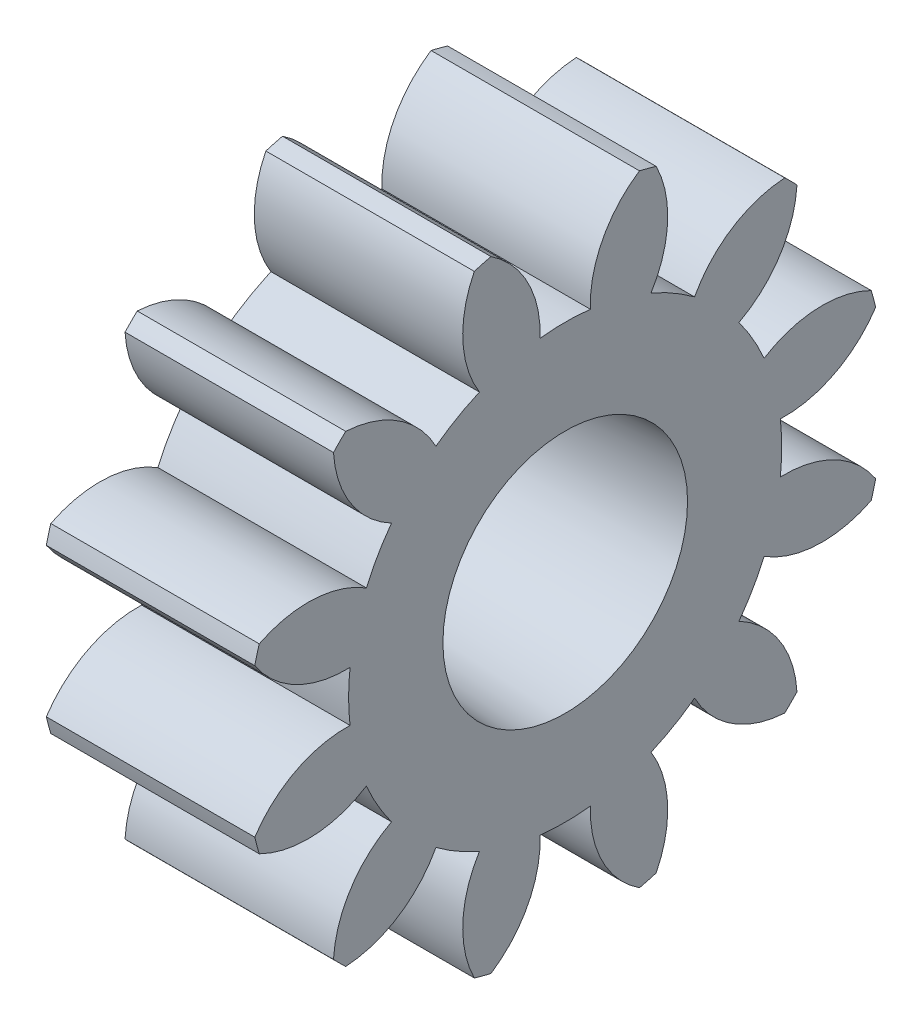
SolidWorks part; units mm, degrees
ref_plane "Plane1" through (0, 0, 0) normal (0, 0, 1) x (1, 0, 0)
ref_plane "Plane2" through (0, 0, 0) normal (0, 1, 0) x (1, 0, 0)
ref_plane "Plane3" through (0, 0, 0) normal (1, 0, 0) x (0, 0, -1)
other "Configuration Table"
sketch "HoldingSke" plane through (0, 0, 0) normal (0, 1, 0) x (1, 0, 0)
  line L0 (0, 0) -> (0.5589, -0.1188)
  line L1 (-15, 0) -> (100, 0) construction
  line L2 (0, 0) -> (-2.1039, 2.3779)
  line L3 (0, 0) -> (-11.863, 4.5341)
  line L4 (0, 0) -> (8.4473, 1.7955)
  line L5 (0, 0) -> (-14.9912, -5.5913)
  line L6 (0, 0) -> (-6.6317, -4.4744)
  line L7 (-2.1039, 2.3779) -> (1.3401, 18.0029)
  line L8 (-76.2, 54.61) -> (-74.8, 54.61)
  line L9 (-71.009, 38.7566) -> (-53.1078, 45.2721)
  line L10 (-76.2, 71.12) -> (104.1128, 71.12)
  line L11 (0, 0) -> (-8, 0)
  line L12 (-76.2, 101.6) -> (-76.147, 101.6)
  line L13 (24.9733, 27.94) -> (52.9518, 28.4284)
  line L14 (24.9733, 27.94) -> (24.9743, 27.94)
  line L15 (24.9733, 27.94) -> (100.4006, 29.5858)
  line L16 (-63.627, -1.75) -> (-12.827, -1.75)
  circle A0 centre (0, 0) radius 4.5
  circle A1 centre (0, 0) radius 8.3115
  circle A2 centre (0, 0) radius 37.5
  circle A3 centre (0, 0) radius 4.5
  dimension "Num_teeth" = 12
  dimension "Pitch_radius" = 180.3128
  dimension "Width" = 8
  dimension "Thickness" = 8
sketch "BasProSke" plane through (0, 0, 0) normal (0, 1, 0) x (1, 0, 0)
  line L0 (-10, 0) -> (60, 0) construction
  line L1 (0, 0) -> (0, 12.25)
  line L2 (0, 0) -> (8, 0)
  line L3 (8, 0) -> (8, 12.25)
  line L4 (8, 12.25) -> (0, 12.25)
  dimension "Thickness" = 8
  dimension "Diameter" = 24.5
revolve "Base-Revolve" add sketch "BasProSke" angle 360 about L0
sketch "TooCutSke" plane through (0, 0, 0) normal (1, 0, 0) x (0, 0, -1)
  line L1 (0, 0) -> (0, 107) construction
  line L2 (0, 0) -> (-1.4632, 10.3976) construction
  line L3 (0, 0) -> (-5.3948, 20.1337) construction
  line L4 (-1.4632, 10.3976) -> (-2.6974, 10.0668) construction
  arc A0 (0.9651, 8.2553) -> (-0.9651, 8.2553) centre (0, 0) ccw
  arc A1 (2.8783, 11.9332) -> (-2.8783, 11.9332) centre (0, 0) ccw
  circle A2 centre (0, 0) radius 10.5 construction
  circle A3 centre (0, 0) radius 9.8668 construction
  arc A4 (-0.9651, 8.2553) -> (-2.8783, 11.9332) centre (-5.1623, 8.4085) ccw
  arc A5 (2.8783, 11.9332) -> (0.9651, 8.2553) centre (5.1623, 8.4085) ccw
extrude "ToothCut" cut sketch "TooCutSke" along normal through all
fillet "Breaks" [suppressed] radius 0.035 tangent propagation no
fillet "RootFillets" [suppressed] radius 0.4385
pattern_circular "TeethCuts" count 12 every 30 about axis through (-10, 0, 0) along (1, 0, 0) of "ToothCut", "RootFillets", "Breaks"
sketch "HubNeaOneSke" plane through (0, 0, 0) normal (-1, 0, 0) x (0, 0, 1)
  circle A0 centre (0, 0) radius 8.3115
  dimension "Diameter" = 16.623
extrude "HubNearOne" add sketch "HubNeaOneSke" along normal blind 8.0001
sketch "HubNeaBotSke" plane through (0, 0, 0) normal (-1, 0, 0) x (0, 0, 1)
  circle A0 centre (0, 0) radius 8.3115
  dimension "Diameter" = 16.623
extrude "HubNearBoth" [suppressed] add sketch "HubNeaBotSke" along normal blind 4
ref_plane "FarPln" through (8, 0, 0) normal (1, 0, 0) x (0, 0, -1)
sketch "HubFarSke" plane through (8, 0, 0) normal (1, 0, 0) x (0, 0, -1)
  circle A0 centre (0, 0) radius 8.3115
  dimension "Diameter" = 16.623
extrude "HubFar" [suppressed] add sketch "HubFarSke" along normal blind 4
sketch "BorSke" plane through (0, 0, 0) normal (1, 0, 0) x (0, 0, -1)
  circle A0 centre (0, 0) radius 4.5
  dimension "Diameter" = 9
extrude "Bore" cut sketch "BorSke" along normal mid plane 32.0001
sketch "KeySke" plane through (0, 0, 0) normal (1, 0, 0) x (0, 0, -1)
  line L0 (-1.5, 0) -> (-1.5, 5.9)
  line L1 (-1.5, 5.9) -> (1.5, 5.9)
  line L2 (1.5, 5.9) -> (1.5, 0)
  line L3 (0, 0) -> (0, 34) construction
  line L4 (-1.5, 0) -> (1.5, 0)
  dimension "Width" = 3
extrude "Keyway" [suppressed] cut sketch "KeySke" along normal mid plane 32.0001
pattern_circular "Keyway2" [suppressed] count 2 every 90 about axis through (-10, 0, 0) along (1, 0, 0) reverse direction yes
sketch "Esquisse1" plane through (-8.0001, 0, 0) normal (-1, 0, 0) x (0, 0, 1)
  circle A0 centre (0, 0) radius 8.3115
extrude "Enlèv. mat.-Extru.1" cut sketch "Esquisse1" against normal blind 8
sketch "Esquisse2" plane through (8, 0, 0) normal (1, 0, 0) x (0, 0, -1)
  circle A0 centre (0, 0) radius 4.275
  circle A1 centre (0, 0) radius 4.5
  dimension "D1" = 8.55
extrude "Boss.-Extru.1" add sketch "Esquisse2" against normal blind 8
sketch "Esquisse3" plane through (-0.0001, 0, 0) normal (-1, 0, 0) x (0, 0, 1)
  circle A0 centre (0, 0) radius 4.275
extrude "Enlèv. mat.-Extru.2" cut sketch "Esquisse3" against normal blind 10 draft 3 draft outward yes
equation "' \"Module@HoldingSke\" = 6.35"
equation "' \"Num_teeth@HoldingSke\" = 12"
equation "' \"Ap@HoldingSke\" =  20"
equation "' \"Ap@HoldingSke\" = 20"
equation "' \"Width@HoldingSke\" = 0.5 * 25.4"
equation "' \"Hub_dia@HoldingSke\"= 1 * 25.4"
equation "' \"Hub_dia@HoldingSke\" = 1 * 25.4"
equation "' \"Overall_len@HoldingSke\" = 1.0 * 25.4"
equation "' \"Bore@HoldingSke\" = 0.75 * 25.4"
equation "' \"T_dim@HoldingSke\" = 0.1 * 25.4"
equation "' \"Width@KeySke\" = 0.25 * 25.4"
equation "' \"Show_teeth@HoldingSke\" = 13"
equation "' \"Backlash@HoldingSke\" = 0.009 * 25.4"
equation "' \"Addendum_fac@HoldingSke\" = 1.0"
equation "' \"Dedendum_fac@HoldingSke\" = 1.25"
equation "' \"Dedendum_add@HoldingSke\" = 0.00005 * 25.4"
equation "' \"Clearance_fac@HoldingSke\" = 0.25"
equation "\"Pitch@HoldingSke\" = 1 / \"Module@HoldingSke\""
equation "\"Overcut_dia@TooCutSke\" = (\"Num_teeth@HoldingSke\" + 2 * \"Addendum_fac@HoldingSke\") / \"Pitch@HoldingSke\" + 0.002 * 25.4"
equation "\"Pitch_dia@TooCutSke\" = \"Num_teeth@HoldingSke\" / \"Pitch@HoldingSke\""
equation "\"Base_dia@TooCutSke\" = \"Num_teeth@HoldingSke\" / \"Pitch@HoldingSke\" * cos((\"Ap@HoldingSke\"  * 3.14159265 / 180))"
equation "\"Root_dia@TooCutSke\" = (\"Num_teeth@HoldingSke\" + 2) / \"Pitch@HoldingSke\" - 2 * (\"Addendum_fac@HoldingSke\" + \"Dedendum_fac@HoldingSke\") / \"Pitch@HoldingSke\" - \"Dedendum_add@HoldingSke\" * 2"
equation "\"Half_ang@TooCutSke\" = 180 / \"Num_teeth@HoldingSke\""
equation "\"Half_CT@TooCutSke\" = \"Num_teeth@HoldingSke\" / \"Pitch@HoldingSke\" * sin((3.14159265 / 2 / \"Num_teeth@HoldingSke\")) / 2 - 7 * \"Backlash@HoldingSke\" / 4"
equation "\"Flank_rad@TooCutSke\" = \"Num_teeth@HoldingSke\" / \"Pitch@HoldingSke\" / 5"
equation "\"Radius@RootFillets\" = \"Clearance_fac@HoldingSke\" / \"Pitch@HoldingSke\" + \"Dedendum_add@HoldingSke\""
equation "\"Break_rad@Breaks\" = 0.02 / \"Pitch@HoldingSke\""
equation "\"Thickness@HoldingSke\" = \"Width@HoldingSke\""
equation "\"OAL@HoldingSke\" = \"Thickness@HoldingSke\""
equation "\"MHD@HoldingSke\" = (\"Num_teeth@HoldingSke\" + 2) / \"Pitch@HoldingSke\" - 2 * (\"Addendum_fac@HoldingSke\" + \"Dedendum_fac@HoldingSke\")  / \"Pitch@HoldingSke\" - \"Dedendum_add@HoldingSke\" * 2"
equation "\"MBD@HoldingSke\" = (\"Num_teeth@HoldingSke\" + 2) / \"Pitch@HoldingSke\" - 2 * (\"Addendum_fac@HoldingSke\" + \"Dedendum_fac@HoldingSke\")  / \"Pitch@HoldingSke\" - \"Dedendum_add@HoldingSke\" * 2 - 0.002 * 25.4"
equation "\"MHD@HoldingSke\" = ((sgn( \"MHD@HoldingSke\" - \"Hub_dia@HoldingSke\" )-1)*( \"MHD@HoldingSke\" - \"Hub_dia@HoldingSke\" ))/-2+ \"Hub_dia@HoldingSke\""
equation "\"MBD@HoldingSke\" = ((sgn( \"MBD@HoldingSke\" - \"Bore@HoldingSke\" )-1)*( \"MBD@HoldingSke\" - \"Bore@HoldingSke\" ))/-2+ \"Bore@HoldingSke\""
equation "\"OAL@HoldingSke\" = ((sgn( \"OAL@HoldingSke\" - \"Overall_len@HoldingSke\" )+1)*( \"OAL@HoldingSke\" - \"Overall_len@HoldingSke\" ))/2 + \"Overall_len@HoldingSke\" + 0.000002 * 25.4"
equation "\"Num_teeth@TeethCuts\" = int( \"Show_teeth@HoldingSke\" ) + 1"
equation "\"Num_teeth@TeethCuts\" = ((sgn( \"Num_teeth@TeethCuts\" - \"Num_teeth@HoldingSke\" )-1)*( \"Num_teeth@TeethCuts\" - \"Num_teeth@HoldingSke\" ))/-2+ \"Num_teeth@HoldingSke\""
equation "\"Num_teeth@TeethCuts\" = ((sgn( \"Num_teeth@TeethCuts\" - 2.0)+1)*( \"Num_teeth@TeethCuts\" - 2.0))/2 +2.0"
equation "\"Angle@TeethCuts\" = 360.0 / \"Num_teeth@HoldingSke\""
equation "\"Diameter@BasProSke\" = (\"Num_teeth@HoldingSke\" + 2 * \"Addendum_fac@HoldingSke\") / \"Pitch@HoldingSke\""
equation "\"Thickness@BasProSke\"  = \"Thickness@HoldingSke\""
equation "' \"Fillet_rad@BasProSke\" =  \"Thickness@HoldingSke\" * 0.05"
equation "' \"Fillet_rad@BasProSke\" = \"Thickness@HoldingSke\" * 0.05"
equation "\"MHD@HoldingSke\" = ((sgn( \"MHD@HoldingSke\" - \"Root_dia@TooCutSke\" )-1)*( \"MHD@HoldingSke\" - \"Root_dia@TooCutSke\" ))/-2+ \"Root_dia@TooCutSke\""
equation "\"Diameter@HubNeaOneSke\" = \"MHD@HoldingSke\""
equation "\"Length@HubNearOne\" = \"OAL@HoldingSke\" - \"Thickness@BasProSke\""
equation "\"Diameter@HubNeaBotSke\" = \"MHD@HoldingSke\""
equation "\"Length@HubNearBoth\" = ( \"OAL@HoldingSke\" - \"Thickness@BasProSke\" ) / 2.0"
equation "\"Thickness@FarPln\" = \"Thickness@BasProSke\""
equation "\"Diameter@HubFarSke\" = \"MHD@HoldingSke\""
equation "\"Length@HubFar\" = ( \"OAL@HoldingSke\" - \"Thickness@BasProSke\" ) / 2.0"
equation "\"Diameter@BorSke\" = \"MBD@HoldingSke\""
equation "\"D1@Bore\" = \"OAL@HoldingSke\" * 2.0"
equation "\"D1@Keyway\" = \"OAL@HoldingSke\" * 2.0"
equation "\"Offset@KeySke\" = \"T_dim@HoldingSke\" + \"MBD@HoldingSke\" / 2.0"
